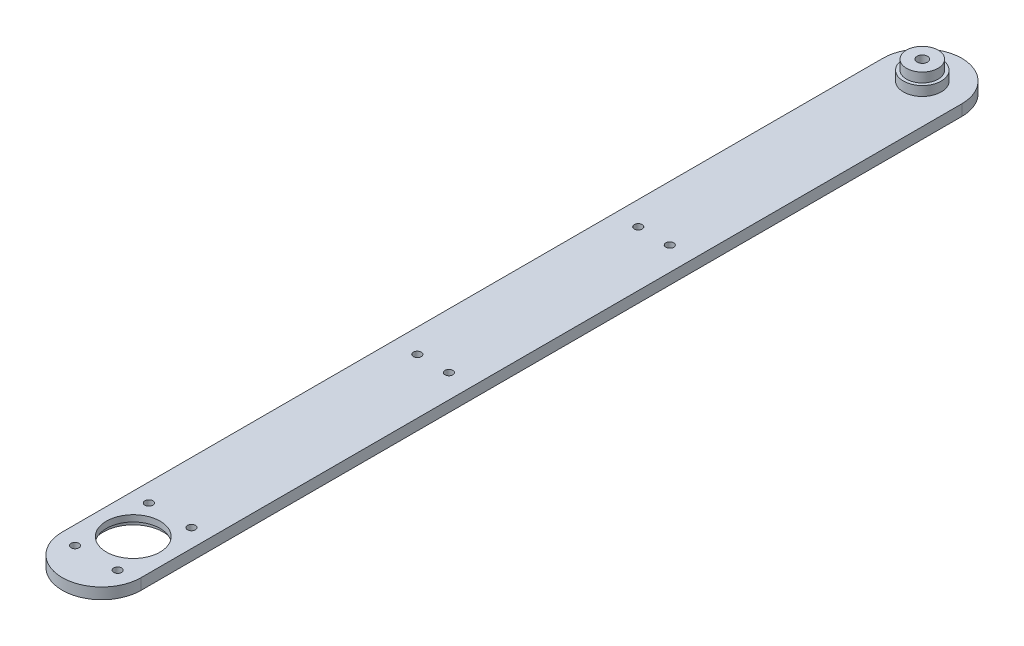
SolidWorks part; units mm, degrees
material "7075-T6 (SN)"
ref_plane "정면" through (0, 0, 0) normal (0, 0, 1) x (1, 0, 0)
ref_plane "윗면" through (0, 0, 0) normal (0, 1, 0) x (1, 0, 0)
ref_plane "우측면" through (0, 0, 0) normal (1, 0, 0) x (0, 0, -1)
sketch "스케치1" plane through (0, 0, 0) normal (0, 1, 0) x (1, 0, 0)
  circle A0 centre (0, 0) radius 5
  dimension "D1" = 10
extrude "보스-돌출1" add sketch "스케치1" along normal blind 10.5 and the other way blind 10.5
sketch "스케치6" plane through (0, 0, 0) normal (0, 1, 0) x (1, 0, 0)
  line L0 (-12.5, 0) -> (-12.5, -260)
  line L1 (0, 0) -> (0, -260) construction
  line L2 (12.5, 0) -> (12.5, -260)
  arc A0 (12.5, 0) -> (-12.5, 0) centre (0, 0) ccw
  arc A1 (-12.5, -260) -> (12.5, -260) centre (0, -260) ccw
  dimension "D1" = 25
  dimension "D3" = 25
  dimension "D2" = 260
extrude "보스-돌출3" add sketch "스케치6" along normal blind 4.5 and the other way blind 4.5
sketch "스케치7" plane through (0, -4.5, 0) normal (0, -1, 0) x (1, 0, 0)
  circle A0 centre (0, 0) radius 6
  dimension "D1" = 12
extrude "보스-돌출4" add sketch "스케치7" along normal blind 3
sketch "스케치8" plane through (0, 4.5, 0) normal (0, 1, 0) x (1, 0, 0)
  circle A0 centre (0, 0) radius 6
  dimension "D1" = 12
extrude "보스-돌출5" add sketch "스케치8" along normal blind 3
sketch "스케치9" plane through (0, -4.5, 0) normal (0, -1, 0) x (1, 0, 0)
  circle A0 centre (0, 250) radius 9.5
  dimension "D1" = 19
  dimension "D2" = 250
extrude "컷-돌출1" cut sketch "스케치9" against normal blind 7
sketch "스케치10" plane through (0, 2.5, 0) normal (0, -1, 0) x (1, 0, 0)
  circle A0 centre (0, 250) radius 8.5
  dimension "D1" = 17
  dimension "D2" = 250
extrude "컷-돌출2" cut sketch "스케치10" against normal through all
hole_wizard "M4 탭을 위한 탭 드릴1" positions "스케치21" profile "스케치17" hole size "M4" standard "ISO" end condition through all
sketch "스케치21" plane through (0, -10.5, 0) normal (0, -1, 0) x (-1, 0, 0)
  point P0 (0, 0)
sketch "스케치17" plane through (0, -10.5, 0) normal (1, 0, 0) x (0, 0, -1)
  line L0 (0, 0) -> (0, 21)
  line L1 (0, 21) -> (1.65, 21)
  line L2 (1.65, 21) -> (1.65, 0)
  line L5 (1.65, 0) -> (0, 0)
  line L11 (0, -6.35) -> (0, 107.95) construction
  dimension "관통 구멍 지름" = 3.3
  dimension "관통 구멍 깊이" = 21
sketch "스케치22" plane through (0, 0, 0) normal (0, 0, 1) x (1, 0, 0)
  line L0 (-30.7176, 0) -> (34.448, 0) construction
  line L1 (-23.3733, 1) -> (23.2568, 1)
  line L2 (-23.3733, 1) -> (-23.3733, -19.0144)
  line L3 (-23.3733, -19.0144) -> (23.2568, -19.0144)
  line L4 (23.2568, 1) -> (23.2568, -19.0144)
  dimension "D1" = 1
extrude "컷-돌출3" cut sketch "스케치22" against normal mid plane 2222
sketch "스케치23" plane through (0, 1, 0) normal (0, -1, 0) x (1, 0, 0)
  line L0 (0, 250) -> (0, 283.9893) construction
  line L1 (0, 250) -> (-16.7759, 279.0567) construction
  circle A0 centre (0, 250) radius 13.5 construction
  circle A1 centre (0, 250) radius 8.5 construction
  point P4 (-6.75, 261.6913)
  dimension "D1" = 27
  dimension "D2" = 30
sketch "스케치26" plane through (0, 1, 0) normal (0, -1, 0) x (1, 0, 0)
  line L0 (-26.7725, 15) -> (35.5858, 15) construction
  line L2 (0, 28.0558) -> (0, -32.4838) construction
  line L3 (-5, 53.012) -> (-5, -27.3543) construction
  point P7 (0, 0)
  dimension "D1" = 15
  dimension "D2" = 5
hole_wizard "M3 탭을 위한 탭 드릴2" positions "스케치27" profile "스케치28" hole size "M3" standard "ISO" end condition through all
sketch "스케치27" plane through (0, 1, 0) normal (0, -1, 0) x (-1, 0, 0)
  line L0 (26.7725, -15) -> (-35.5858, -15) construction
  line L1 (5, -53.012) -> (5, 27.3543) construction
  point P0 (5, -15)
sketch "스케치28" plane through (-5, 1, 15) normal (1, 0, 0) x (0, 0, -1)
  line L0 (0, 0) -> (0, 9.5)
  line L1 (0, 9.5) -> (1.25, 9.5)
  line L2 (1.25, 9.5) -> (1.25, 0)
  line L5 (1.25, 0) -> (0, 0)
  line L11 (0, -6.35) -> (0, 107.95) construction
  dimension "관통 구멍 지름" = 2.5
  dimension "관통 구멍 깊이" = 9.5
pattern_linear "선형 패턴1" count 3 spacing 70 along (0, 0, 1) count 2 spacing 10 along (1, 0, 0) of "M3 탭을 위한 탭 드릴2"
hole_wizard "M3 탭을 위한 탭 드릴1" positions "스케치29" profile "스케치31" hole size "M3" standard "ISO" end condition through all
sketch "스케치29" plane through (0, 1, 0) normal (0, -1, 0) x (-1, 0, 0)
  point P0 (6.75, -261.6913)
sketch "스케치31" plane through (-6.75, 1, 261.6913) normal (1, 0, 0) x (0, 0, -1)
  line L0 (0, 0) -> (0, 9.5)
  line L1 (0, 9.5) -> (1.25, 9.5)
  line L2 (1.25, 9.5) -> (1.25, 0)
  line L5 (1.25, 0) -> (0, 0)
  line L11 (0, -6.35) -> (0, 107.95) construction
  dimension "관통 구멍 지름" = 2.5
  dimension "관통 구멍 깊이" = 9.5
pattern_circular "원형 패턴1" count 6 over 360 about axis through (0, 2.5, 250) along (0, -1, 0) skipping 1, 4 of "M3 탭을 위한 탭 드릴1"
sketch "스케치32" plane through (0, 1, 0) normal (0, -1, 0) x (1, 0, 0)
  circle A0 centre (-5, 15) radius 1.25
  circle A1 centre (-5, 15) radius 1.25 construction
  circle A2 centre (5, 15) radius 1.25
  circle A3 centre (5, 15) radius 1.25 construction
extrude "보스-돌출6" add sketch "스케치32" against normal blind 3.5
